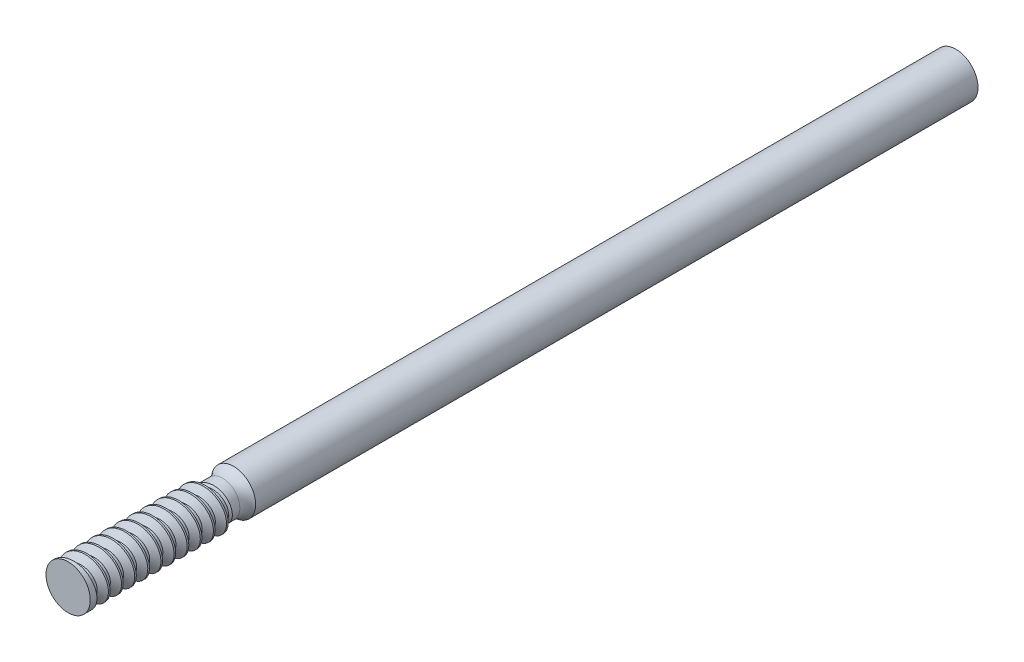
SolidWorks part; units mm, degrees
ref_plane "Front Plane" through (0, 0, 0) normal (0, 0, 1) x (1, 0, 0)
ref_plane "Top Plane" through (0, 0, 0) normal (0, 1, 0) x (1, 0, 0)
ref_plane "Right Plane" through (0, 0, 0) normal (1, 0, 0) x (0, 0, -1)
sketch "Sketch1" plane through (0, 0, 0) normal (0, 0, 1) x (1, 0, 0)
  circle A0 centre (0, 0) radius 3.5687
  dimension "ShaftOD" = 7.1374
extrude "Boss-Extrude1" add sketch "Sketch1" along normal blind 143.1544
thread "Thread1" pitch 2.1167 method cut profile "Thread Profile1" start angle 0, offset 0, length 22.86, pitch 2.1167, diameter 7.1374
ref_plane "Plane1" through (-3.5687, 0, 143.1544) normal (0, -1, 0) x (-1, 0, 0)
sketch "Thread Profile1" plane through (-3.5687, 0, 143.1544) normal (0, -1, 0) x (-1, 0, 0)
  line L0 (0, 0) -> (0, 2.1167) construction
  line L11 (0, 0) -> (0, 1.8521)
  line L12 (0, 1.8521) -> (-1.1457, 1.1906)
  line L13 (-1.1457, 1.1906) -> (-1.1457, 0.6615)
  line L15 (-1.1457, 0.6615) -> (0, 0)
  line L17 (-1.1457, 0.926) -> (0, 0.926) construction
  point P2 (0, 0)
  dimension "Pitch" = 2.1167
  dimension "Profile_Angle" = 60
  dimension "Profile_Land" = 0.5292
  dimension "Profile_Height" = 1.1457
sketch "Sketch12" plane through (0, 0, 143.1544) normal (0, 0, 1) x (1, 0, 0)
  circle A0 centre (0, 0) radius 2.8194
  circle A1 centre (0, 0) radius 3.5687
  circle A2 centre (0, 0) radius 3.5687 construction
  dimension "D1" = 5.6388
extrude "Cut-Extrude1" cut sketch "Sketch12" against normal blind 3.81 from offset 22.86 offset against normal yes
fillet "Fillet1" radius 2.54 1 edges at (2.8194, 0, 116.4844)
